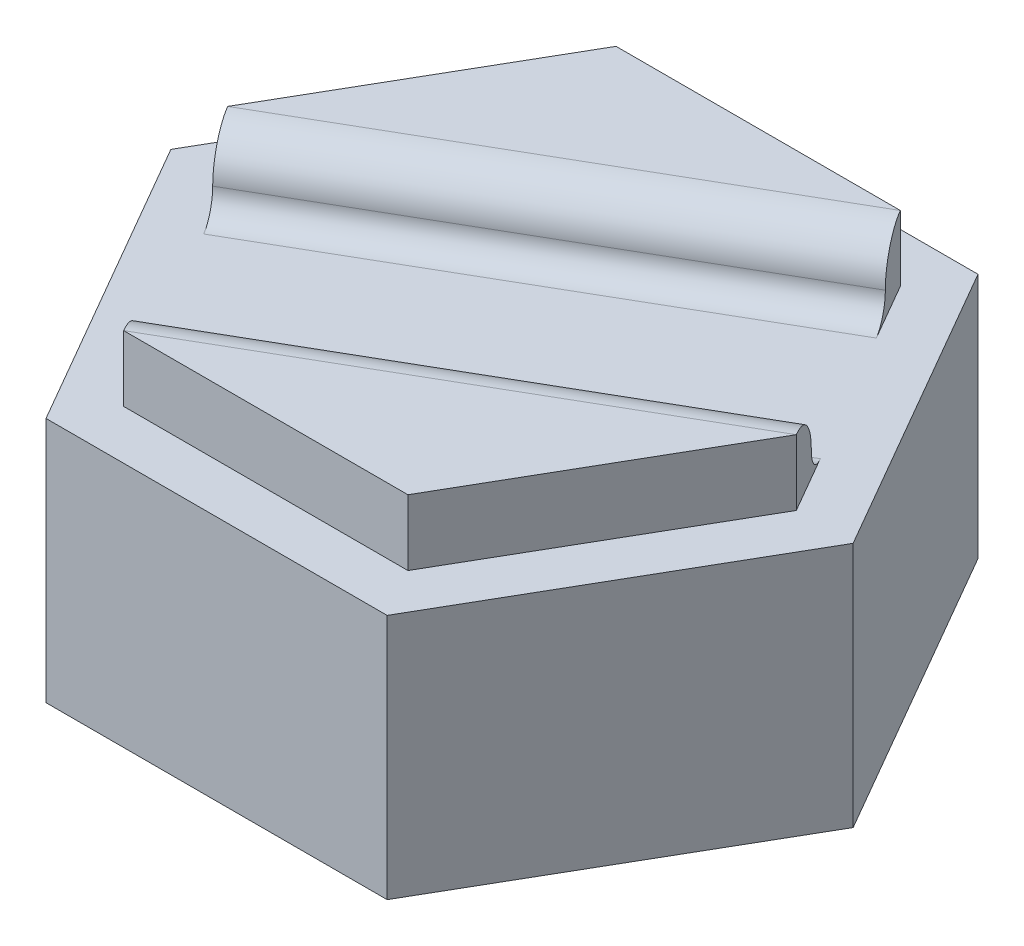
SolidWorks part; units mm, degrees
ref_plane "Front Plane" through (0, 0, 0) normal (0, 0, 1) x (1, 0, 0)
ref_plane "Top Plane" through (0, 0, 0) normal (0, 1, 0) x (1, 0, 0)
ref_plane "Right Plane" through (0, 0, 0) normal (1, 0, 0) x (0, 0, -1)
sketch "Sketch1" plane through (0, 0, 0) normal (0, 1, 0) x (1, 0, 0)
  line L1 (10.3923, 0) -> (5.1962, 9)
  line L2 (5.1962, 9) -> (-5.1962, 9)
  line L3 (-5.1962, 9) -> (-10.3923, 0)
  line L4 (-10.3923, 0) -> (-5.1962, -9)
  line L5 (-5.1962, -9) -> (5.1962, -9)
  line L6 (5.1962, -9) -> (10.3923, 0)
  line L7 (8.6603, 0) -> (4.3301, 7.5)
  line L8 (4.3301, 7.5) -> (-4.3301, 7.5)
  line L9 (-4.3301, 7.5) -> (-8.6603, 0)
  line L10 (-8.6603, 0) -> (-4.3301, -7.5)
  line L11 (-4.3301, -7.5) -> (4.3301, -7.5)
  line L12 (4.3301, -7.5) -> (8.6603, 0)
  circle A0 centre (0, 0) radius 9 construction
  circle A1 centre (0, 0) radius 7.5 construction
  dimension "D1" = 18
  dimension "D2" = 1.5
extrude "Boss-Extrude1" add sketch "Sketch1" along normal blind 7.5 contours L11 L12 L7 L8 L9 L10 | L5 L6 L1 L2 L3 L4 L12 L11 L10 L9 L8 L7 region at (7.5561, 0, 4.3625) region at (0, 0, 0)
extrude "Cut-Extrude1" cut sketch "Sketch1<3>" along normal blind 2 contours L11 L12 L7 L8 L9 L10 region at (0, 0, 0)
sketch "Sketch1<3>" plane through (0, 0, 0) normal (0, 1, 0) x (1, 0, 0) same geometry as "Sketch1"
sketch "Sketch4" plane through (0, 7.5, 0) normal (0, 1, 0) x (1, 0, 0)
  line L0 (10.3923, 0) -> (5.1962, 9) construction
  line L1 (8.6603, 0) -> (4.3301, 7.5)
  line L2 (4.3301, 7.5) -> (-4.3301, 7.5)
  line L3 (-4.3301, 7.5) -> (-8.6603, 0)
  line L4 (-8.6603, 0) -> (-4.3301, -7.5)
  line L5 (-4.3301, -7.5) -> (4.3301, -7.5)
  line L6 (4.3301, -7.5) -> (8.6603, 0)
  circle A0 centre (0, 0) radius 7.5 construction
  dimension "D1" = 1.5
extrude "Boss-Extrude2" add sketch "Sketch4" along normal blind 2
sketch "Sketch5" plane through (-6.4952, 0, 3.75) normal (-0.866, 0, 0.5) x (0.5, 0, 0.866)
  line L0 (-4.3301, 7.5) -> (-2.3301, 7.5)
  line L1 (-4.3301, 7.5) -> (4.3301, 7.5) construction
  line L2 (-4.3301, 7.5) -> (-4.3301, 9.5)
  line L3 (-4.3301, 8.25) -> (-3.0801, 8.25) construction
  line L4 (0, 7.5) -> (0, 9.5) construction
  line L5 (-4.3301, 9.5) -> (4.3301, 9.5) construction
  line L6 (4.3301, 7.5) -> (4.3301, 9.5)
  line L7 (4.3301, 7.5) -> (2.3301, 7.5)
  line L9 (-4.3301, 9.5) -> (4.3301, 9.5)
  line L10 (-4.3301, 9.5) -> (-4.3301, 7.5)
  line L11 (-4.3301, 7.5) -> (4.3301, 7.5)
  line L12 (4.3301, 9.5) -> (4.3301, 7.5)
  arc A1 (-3.0801, 8.25) -> (-4.3301, 9.5) centre (-4.3301, 8.25) ccw
  arc A2 (-3.0801, 8.25) -> (-2.3301, 7.5) centre (-2.3301, 8.25) ccw
  arc A3 (3.0801, 8.25) -> (4.3301, 9.5) centre (4.3301, 8.25) cw
  arc A4 (3.0801, 8.25) -> (2.3301, 7.5) centre (2.3301, 8.25) cw
  line M7 (-4.3301, 7.5) -> (4.3301, 7.5)
  line M9 (4.3301, 9.5) -> (-4.3301, 9.5)
  dimension "D2" = 2.5
  dimension "D1" = 2
extrude "Cut-Extrude2" cut sketch "Sketch5" against normal up to surface (15 mm away) contours A4 A3 A1 A2 M9 M7 region at (-6.4952, 8.5537, 3.75) up to face at (6.4952, 8.5, -3.75)
sketch "Sketch6" plane through (-7.7942, 0, 4.5) normal (-0.866, 0, 0.5) x (0.5, 0, 0.866)
  line L0 (0, 7.5) -> (0, 0) construction
  line L1 (-5.1962, 7.5) -> (5.1962, 7.5) construction
  line L3 (-4.3301, 4.7737) -> (-3.3301, 4.7737)
  line L4 (-4.3301, 4.7737) -> (-4.3301, 3.7737)
  line L5 (-4.3301, 3.7737) -> (-3.3301, 3.7737)
  line L6 (-3.3301, 4.7737) -> (-3.3301, 3.7737)
  line L14 (-4.3301, 9.5) -> (-4.3301, 7.5) construction
  dimension "D1" = 1
  dimension "D2" = 1
  dimension "D3" = 3.3301
extrude "Cut-Extrude3" cut sketch "Sketch6" against normal blind 2
sketch "Sketch7" plane through (-2.1651, 0, -3.75) normal (0.5, 0, 0.866) x (0.866, 0, -0.5)
  line L1 (-7, 3.7737) -> (-7.5, 3.7737)
  line L2 (-7, 3.7737) -> (-7, 3.2737)
  line L3 (-7, 3.2737) -> (-7.5, 3.2737)
  line L4 (-7.5, 3.7737) -> (-7.5, 3.2737)
  dimension "D1" = 0.5
  dimension "D2" = 0.5
extrude "Cut-Extrude4" cut sketch "Sketch7" along normal up to surface (1 mm away) up to face at (-8.5933, 4.2737, 1.116)
ref_plane "Plane1" through (0, 0, 0) normal (-0.5, 0, -0.866) x (0, -1, 0)
mirror "Mirror1" about plane through (0, 0, 0) normal (-0.5, 0, -0.866) of "Cut-Extrude4", "Cut-Extrude3"
